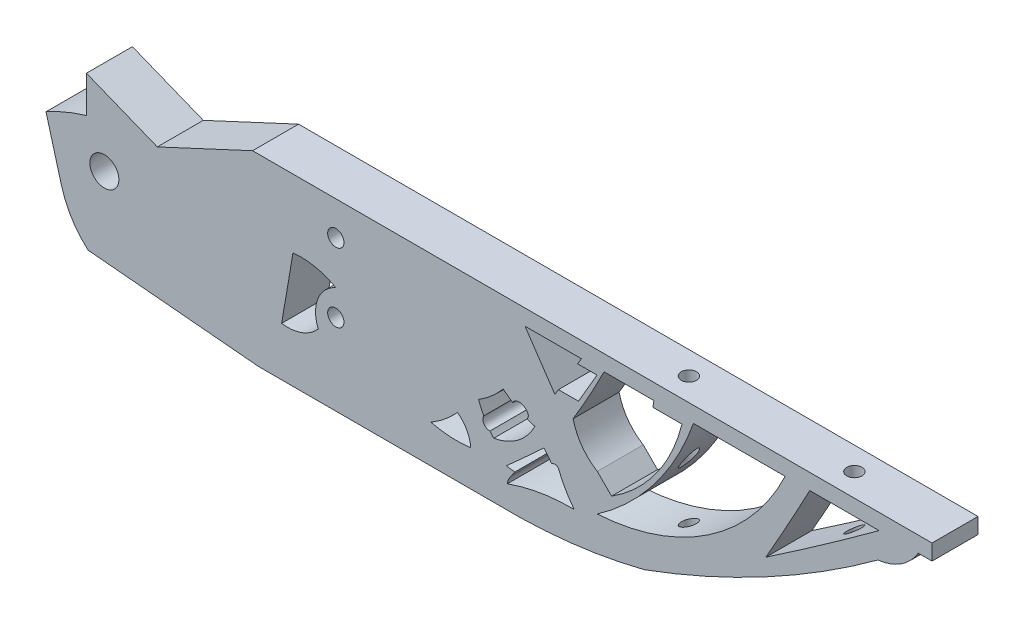
SolidWorks part; units mm, degrees
ref_plane "Front Plane" through (0, 0, 0) normal (0, 0, 1) x (1, 0, 0)
ref_plane "Top Plane" through (0, 0, 0) normal (0, 1, 0) x (1, 0, 0)
ref_plane "Right Plane" through (0, 0, 0) normal (1, 0, 0) x (0, 0, -1)
sketch "Sketch1" plane through (0, 0, 0) normal (0, 0, 1) x (1, 0, 0)
  line L1 (120.65, 25.4) -> (-120.65, 25.4)
  line L2 (120.65, 25.4) -> (120.65, -25.4)
  line L3 (120.65, -25.4) -> (-120.65, -25.4)
  line L4 (-120.65, 25.4) -> (-120.65, -25.4)
  line L5 (120.65, 25.4) -> (-120.65, -25.4) construction
  line L6 (120.65, -25.4) -> (-120.65, 25.4) construction
  point P0 (0, 0)
  dimension "D1" = 241.3
  dimension "D2" = 50.8
extrude "Boss-Extrude1" add sketch "Sketch1" along normal blind 12.7
sketch "Sketch3" plane through (0, 0, 12.7) normal (0, 0, 1) x (1, 0, 0)
  line L0 (0, 0) -> (-120.65, 0) construction
  line L1 (-120.65, 25.4) -> (-120.65, -25.4) construction
  circle A0 centre (-107.95, 0) radius 4
  dimension "D2" = 8
  dimension "D1" = 12.7
extrude "Cut-Extrude1" cut sketch "Sketch3" against normal through all
sketch "Sketch5" plane through (0, 0, 12.7) normal (0, 0, 1) x (1, 0, 0)
  line L0 (-120.65, -25.4) -> (120.65, -25.4) construction
  line L1 (-111.232, -5.4361) -> (-109.6883, -6.1074)
  line L2 (-107.95, 6.35) -> (-67.0151, 25.4)
  line L3 (120.65, 25.4) -> (-120.65, 25.4) construction
  line L4 (-67.0151, 25.4) -> (-120.65, 25.4)
  line L5 (-120.65, 25.4) -> (-120.65, -25.4)
  line L6 (-120.65, -25.4) -> (-65.3282, -25.4)
  line L7 (120.65, 13.8537) -> (120.65, -25.4)
  line L8 (120.65, -25.4) -> (0, -25.4)
  line L9 (120.65, 13.8537) -> (105.7036, 13.8537)
  line L13 (-112.4482, 4.482) -> (-117.3177, 9.3339)
  line L14 (-112.4482, -21.1143) -> (-65.3282, -25.4)
  arc A0 (0, -25.4) -> (105.7036, 13.8537) centre (3.5611, 126.9584) ccw
  arc A1 (-109.9582, -6.0241) -> (-114.0227, -1.8561) centre (-107.95, 0) ccw construction
  arc A2 (-107.95, 6.35) -> (-112.4482, 4.482) centre (-107.95, 0) ccw
  arc A5 (-117.3177, 9.3339) -> (-112.4482, -21.1143) centre (-96.4004, -2.9344) ccw
  point P15 (-116.1445, -2.9908)
  line M3 (-120.65, 25.4) -> (-120.65, -25.4)
  line M4 (-120.65, -25.4) -> (120.65, -25.4)
  line M5 (120.65, -25.4) -> (120.65, 25.4)
  line M6 (120.65, 25.4) -> (-120.65, 25.4)
  dimension "D1" = 152.4
  dimension "D2" = 12.7
  dimension "D3" = 45.1505
  dimension "D4" = 45.9039
extrude "Cut-Extrude2" cut sketch "Sketch5" against normal through all contours A2 L2 L1 M6 M3 M4 | A0 L8 M5 | A5 L5 L14 M4 region at (-102.0317, 17.7416, 12.7) region at (-105.9894, -22.0132, 12.7) region at (91.2141, -11.3337, 12.7)
sketch "Sketch6" plane through (0, 0, 12.7) normal (0, 0, 1) x (1, 0, 0)
  line L0 (-107.95, 0) -> (87.8661, 0) construction
  arc A0 (7.1222, -25.4) -> (105.7036, 13.8537) centre (3.5611, 126.9584) ccw construction
  circle A1 centre (19.05, 0) radius 3.1347
  dimension "D1" = 127
sketch "Sketch7" plane through (0, 0, 0) normal (0, 0, -1) x (-1, 0, 0)
  line L0 (44.0204, -2.9977) -> (44.0204, 16.0523) construction
  point P3 (44.0204, -2.9977)
  point P4 (44.0204, 16.0523)
  dimension "D1" = 19.05
sketch "Sketch8" plane through (0, 0, 0) normal (0, 0, -1) x (-1, 0, 0)
  point P0 (44.0204, 16.0523)
  point P3 (44.0204, -2.9977)
hole_wizard "#8 Clearance Hole1" positions "Sketch8" profile "Sketch9" hole size "#8" standard "ANSI Inch" end condition through all
sketch "Sketch9" plane through (-44.0204, 16.0523, 0) normal (1, 0, 0) x (0, 1, 0)
  line L0 (0, 0) -> (0, 12.7)
  line L1 (0, 12.7) -> (2.2479, 12.7)
  line L2 (2.2479, 12.7) -> (2.2479, 0)
  line L5 (2.2479, 0) -> (0, 0)
  line L11 (0, -6.35) -> (0, 107.95) construction
  dimension "Thru Hole Dia." = 4.4958
  dimension "Thru Hole Depth" = 12.7
ref_plane "Plane1" through (-114.3, 0, 0) normal (-1, 0, 0) x (0, 0, 1)
sketch "Sketch10" plane through (-114.3, 0, 0) normal (-1, 0, 0) x (0, 0, 1)
  line L0 (0, 0) -> (12.7, 0) construction
  line L1 (12.7, -3.1347) -> (12.7, 3.1347) construction
  circle A0 centre (6.0894, 0) radius 1.905
  dimension "D1" = 3.81
sketch "Sketch11" plane through (0, 0, 12.7) normal (0, 0, 1) x (1, 0, 0)
  line L0 (-93.8249, 12.9234) -> (-109.4459, 12.9234) construction
  line L1 (-107.95, 6.35) -> (-67.0151, 25.4) construction
  line L2 (-109.4459, 12.9234) -> (-109.4459, 11.5568) construction
  line L3 (-93.8249, 12.9234) -> (-109.4459, 5.6538)
  line L10 (-119.777, -9.3826) -> (-115.4906, -1.5141)
  line L11 (-115.4906, -1.5141) -> (-109.4459, 5.6538)
  line L12 (-124.0726, 6.1903) -> (-119.777, -9.3826)
  arc A0 (-117.3177, 9.3339) -> (-112.4482, -21.1143) centre (-96.4004, -2.9344) ccw construction
  circle A1 centre (-107.95, 0) radius 4 construction
  arc A4 (-124.0726, 6.1903) -> (-93.8249, 12.9234) centre (-97.649, -41.2057) cw
  dimension "D2" = 5.6538
extrude "Boss-Extrude2" add sketch "Sketch11" against normal up to surface (12.7 mm away) up to face at (-46.2683, 16.0523, 0)
sketch "Sketch18" plane through (0, 25.4, 0) normal (0, 1, 0) x (1, 0, 0)
  circle A0 centre (92.8548, -6.35) radius 2.0828
extrude "Cut-Extrude9" cut sketch "Sketch18" against normal through all contours A0
sketch "Sketch19" plane through (0, 0, 12.7) normal (0, 0, 1) x (1, 0, 0)
  line L3 (86.8867, 21.0579) -> (106.0483, 21.0579)
  line L4 (54.7502, 21.0579) -> (80.0838, 21.0579)
  line L5 (43.8283, 21.0579) -> (30.0654, 21.0579)
  line L6 (21.5195, 21.0579) -> (8.2267, 21.0579)
  line L7 (8.2267, 21.0579) -> (16.4852, 8.8568)
  line L8 (16.4852, 8.8568) -> (23.8201, 21.0579)
  line L9 (23.8201, 21.0579) -> (21.5195, 21.0579)
  arc A0 (106.0483, 21.0579) -> (74.7548, -0.9382) centre (-476.4178, 816.4626) cw
  arc A1 (86.8867, 21.0579) -> (74.7548, -0.9382) centre (-617.5859, 395.2635) cw
  arc A2 (80.0838, 21.0579) -> (28.1833, -13.9058) centre (24.5582, 47.4779) cw
  arc A3 (28.1833, -13.9058) -> (54.7502, 21.0579) centre (-12.7332, 44.7595) ccw
  arc A4 (30.0654, 21.0579) -> (21.5195, 5.5624) centre (-173.1779, 123.0437) cw
  arc A5 (43.8283, 21.0579) -> (28.1833, -3.6987) centre (9.3178, 25.5453) cw
  arc A6 (28.1833, -3.6987) -> (21.5195, 5.5624) centre (35.8652, 8.8568) cw
  arc A7 (3.09, -14.9046) -> (13.4624, -5.4583) centre (-508.9074, 557.7064) ccw
  arc A8 (13.4624, -5.4583) -> (18.8338, -14.9046) centre (-5.5007, -22.4915) cw
  arc A9 (18.8338, -14.9046) -> (3.09, -14.9046) centre (10.9619, 32.5583) cw
  arc A10 (2.2235, 3.0165) -> (-4.5776, -2.8864) centre (-19.0872, 20.7005) cw
  arc A11 (2.2235, 3.0165) -> (10.9619, -1.539) centre (16.8059, 20.3296) ccw
  arc A12 (10.9619, -1.539) -> (-0.4071, -10.0726) centre (-3.0644, 5.3078) cw
  arc A13 (-4.5776, -2.8864) -> (-0.4071, -10.0726) centre (15.1613, 3.7659) ccw
  arc A14 (-10.4164, -8.9177) -> (-6.7592, -15.5263) centre (-15.593, -16.0987) cw
  arc A15 (-6.7592, -15.5263) -> (-17.7308, -14.9046) centre (-10.6309, 13.2663) cw
  arc A16 (-17.7308, -14.9046) -> (-10.4164, -8.9177) centre (-33.6495, 12.0056) ccw
extrude "Cut-Extrude10" cut sketch "Sketch19" against normal through all
pattern_linear "LPattern1" [suppressed] count 5 spacing 6.35 of bodies 117
sketch "Sketch20" plane through (0, 0, 12.7) normal (0, 0, 1) x (1, 0, 0)
  line L0 (-112.9039, 9.7778) -> (-112.9039, 20.995)
  line L2 (-112.9039, 20.995) -> (-92.9368, 13.0011)
  line L3 (-92.9368, 13.0011) -> (-112.9039, 9.7778)
extrude "Boss-Extrude3" add sketch "Sketch20" against normal up to vertex (12.7 mm away) up to point (-124.0726, 6.1903, 0)
sketch "Sketch22" plane through (0, 0, 0) normal (0, 0, -1) x (-1, 0, 0)
  line L0 (-120.65, 21.0579) -> (-116.84, 21.0579)
  line L1 (-120.65, 13.8537) -> (-120.65, 25.4) construction
  line L10 (-120.65, 21.0579) -> (-120.65, 13.8537)
  line L11 (-120.65, 13.8537) -> (-105.7036, 13.8537)
  arc A0 (-116.84, 21.0579) -> (-105.7036, 13.8537) centre (-104.0685, 28.5907) ccw
  dimension "D18" = 14.8275
  dimension "D1" = 3.81
extrude "Cut-Extrude12" cut sketch "Sketch22" against normal through all
sketch "Sketch23" plane through (0, 0, 0) normal (0, 0, -1) x (-1, 0, 0)
  line L2 (-120.65, 21.0579) -> (-120.65, 25.4) construction
  arc A5 (-105.7036, 13.8537) -> (-7.1222, -25.4) centre (-3.5611, 126.9584) ccw
  arc A6 (-105.7036, 13.8537) -> (-41.2201, -20.7154) centre (49.027, 225.0536) ccw
  arc M3 (-105.7036, 13.8537) -> (-7.1222, -25.4) centre (-3.5611, 126.9584) ccw
  dimension "D1" = 152.4
  dimension "D2" = 261.8148
  dimension "D3" = 79.4299
extrude "Cut-Extrude13" cut sketch "Sketch23" against normal through all contours A6 M3 region at (74.7893, -5.9071, 0)
sketch "Sketch24" plane through (0, 0, 0) normal (0, 0, -1) x (-1, 0, 0)
  line L0 (44.0204, -2.9977) -> (44.0204, 16.0523) construction
  line L1 (-80.0838, 21.0579) -> (-54.7502, 21.0579) construction
  arc A0 (44.0204, 4.1309) -> (55.876, 6.5273) centre (53.6319, -12.8946) cw
  arc A1 (55.876, 6.5273) -> (59.0043, -11.8919) centre (1722.1416, 280.0452) ccw
  arc A2 (59.0043, -11.8919) -> (48.8565, -8.1533) centre (57.3207, -0.8203) cw
  arc A3 (48.8565, -8.1533) -> (44.0204, 4.1309) centre (40.2964, -4.4292) ccw
  dimension "D1" = 19.5512
  dimension "D2" = 1688.5654
  dimension "D3" = 11.1989
  dimension "D4" = 9.3351
  dimension "D5" = 22.5656
  dimension "D6" = 31.1257
  dimension "D7" = 35.901
  dimension "D8" = 38.1452
  dimension "D9" = 39.5899
  dimension "D10" = 41.2735
  dimension "D11" = 258.9872
extrude "Cut-Extrude14" cut sketch "Sketch24" against normal through all
sketch "Sketch25" plane through (0, 0, 0) normal (0, 0, -1) x (-1, 0, 0)
  line L2 (-16.1464, -7.9047) -> (-15.512, -8.0981)
  line L3 (-4.3499, -16.7759) -> (-5.4267, -15.2335)
  line L4 (-5.4267, -15.2335) -> (-15.512, -8.0981)
  line L6 (-80.0838, 21.0579) -> (-54.7502, 21.0579) construction
  arc A0 (-4.3499, -16.7759) -> (-3.3328, -19.1048) centre (-8.2887, -19.8825) cw
  arc A1 (-16.1464, -7.9047) -> (-17.4118, -8.2208) centre (-16.5158, -9.1168) ccw
  arc A3 (-17.4118, -8.2208) -> (-21.8096, -15.9981) centre (-45.3139, 2.4248) cw
  arc A4 (-21.8096, -15.9981) -> (-3.3328, -19.1048) centre (-21.1264, -68.4326) cw
  arc A5 (-18.8338, -14.9046) -> (-3.09, -14.9046) centre (-10.9619, 32.5583) ccw construction
  dimension "D1" = 5.0165
  dimension "D2" = 1.2671
  dimension "D3" = 29.864
  dimension "D4" = 52.439
  dimension "D5" = 60.7344
  dimension "D6" = 84.2387
  dimension "D7" = 84.9219
  dimension "D8" = 88.6365
  dimension "D9" = 89.5325
  dimension "D10" = 97.7596
  dimension "D11" = 89.9019
  dimension "D12" = 101.6984
  dimension "D13" = 102.7155
  dimension "D14" = 90.5363
  dimension "D15" = 100.6216
  dimension "D16" = 18.6331
extrude "Cut-Extrude15" cut sketch "Sketch25" against normal through all
sketch "Sketch26" plane through (0, 0, 0) normal (0, 0, -1) x (-1, 0, 0)
  line L0 (-8.8542, -0.8638) -> (-9.1783, 0)
  line L1 (107.95, 0) -> (-87.8661, 0) construction
  line L2 (-4.8856, 1.0865) -> (-5.2499, 1.6746)
  arc A0 (-10.9619, -1.539) -> (-2.2235, 3.0165) centre (-16.8059, 20.3296) ccw construction
  arc A1 (-9.1783, 0) -> (-5.2499, 1.6746) centre (-6.6651, -0.4506) cw
  arc A2 (1.4272, -8.8317) -> (3.1791, -6.1088) centre (1.5839, -7.0075) ccw
  arc A3 (0.4071, -10.0726) -> (4.5776, -2.8864) centre (-15.1613, 3.7659) ccw construction
  arc A4 (-8.8542, -0.8638) -> (-4.8856, 1.0865) centre (-12.5523, 11.6742) ccw
  arc A5 (1.4272, -8.8317) -> (3.1791, -6.1088) centre (5.4965, -9.5248) cw
  dimension "D1" = 2.5533
  dimension "D2" = 1.8309
  dimension "D10" = 13.0721
  dimension "D11" = 4.1278
  dimension "D3" = 55.8252
  dimension "D4" = 57.4204
  dimension "D5" = 63.8899
  dimension "D6" = 64.2542
  dimension "D7" = 65.6694
  dimension "D8" = 67.8586
  dimension "D9" = 68.1827
extrude "Cut-Extrude16" cut sketch "Sketch26" against normal through all
sketch "Sketch27" plane through (0, 0, 0) normal (0, 0, -1) x (-1, 0, 0)
  line L0 (-43.5541, 19.3012) -> (-51.5785, 19.3012)
  line L1 (-28.1833, -3.6987) -> (-32.1378, -7.6533)
  line L2 (-43.5541, 19.3012) -> (-43.0572, 19.3012)
  arc A0 (-43.8283, 21.0579) -> (-28.1833, -3.6987) centre (-9.3178, 25.5453) ccw construction
  arc A1 (-51.5785, 19.3012) -> (-32.1378, -7.6533) centre (-8.3802, 29.9697) ccw
  arc A3 (-43.0572, 19.3012) -> (-28.1833, -3.6987) centre (-4.4439, 27.9629) ccw
  dimension "D1" = 44.4962
  dimension "D2" = 39.5729
  dimension "D3" = 54.4698
  dimension "D4" = 62.4942
  dimension "D5" = 62.9911
  dimension "D6" = 73.9105
  dimension "D7" = 97.6681
extrude "Cut-Extrude17" cut sketch "Sketch27" against normal through all
sketch "Sketch28" plane through (0, 0, 0) normal (0, 0, -1) x (-1, 0, 0)
  line L0 (-22.7681, 19.308) -> (-28.1274, 19.308)
  line L1 (-16.4852, 8.8568) -> (-23.8201, 21.0579) construction
  line L2 (-17.4699, 10.4947) -> (-23.0003, 10.4947)
  line L3 (-23.0003, 10.4947) -> (-28.1274, 19.308)
  line L4 (-22.7681, 19.308) -> (-17.4699, 10.4947)
  dimension "D1" = 76.4742
  dimension "D2" = 81.7724
  dimension "D3" = 82.0046
  dimension "D4" = 87.1317
extrude "Cut-Extrude18" cut sketch "Sketch28" against normal through all
sketch "Sketch29" plane through (0, 25.4, 0) normal (0, 1, 0) x (1, 0, 0)
  line L0 (120.65, -12.7) -> (120.65, 0) construction
  circle A0 centre (47.1354, -6.35) radius 2.0828
  point P0 (120.65, -6.35)
  point P3 (47.1354, -6.35)
  dimension "D2" = 4.1656
  dimension "D1" = 73.5146
extrude "Cut-Extrude19" cut sketch "Sketch29" against normal through all contours A0
